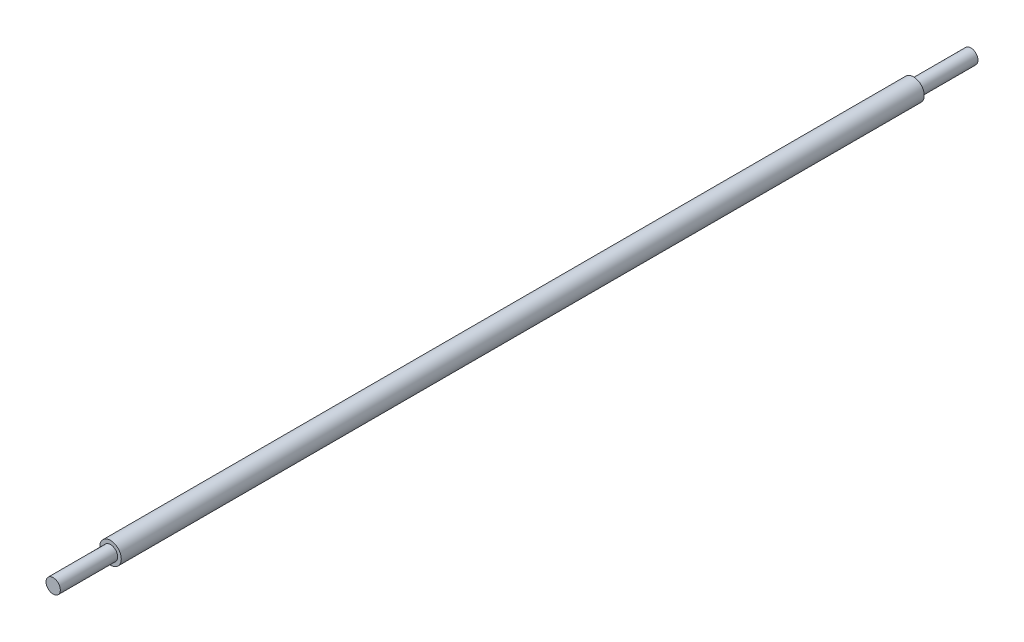
SolidWorks part; units mm, degrees
ref_plane "Front Plane" through (0, 0, 0) normal (0, 0, 1) x (1, 0, 0)
ref_plane "Top Plane" through (0, 0, 0) normal (0, 1, 0) x (1, 0, 0)
ref_plane "Right Plane" through (0, 0, 0) normal (1, 0, 0) x (0, 0, -1)
sketch "Sketch1" plane through (0, 0, 0) normal (0, 0, 1) x (1, 0, 0)
  circle A0 centre (0, 0) radius 2.3813
  dimension "D1" = 4.7625
extrude "Boss-Extrude1" add sketch "Sketch1" along normal blind 203.2
sketch "Sketch2" plane through (0, 0, 0) normal (0, 0, -1) x (-1, 0, 0)
  circle A0 centre (0, 0) radius 1.5875
  circle A1 centre (0, 0) radius 2.3813
  dimension "D1" = 3.175
extrude "Cut-Extrude1" cut sketch "Sketch2" against normal blind 12.7
sketch "Sketch3" plane through (0, 0, 203.2) normal (0, 0, 1) x (1, 0, 0)
  circle A0 centre (0, 0) radius 1.5875
  circle A1 centre (0, 0) radius 2.3813
  dimension "D1" = 3.175
extrude "Cut-Extrude2" cut sketch "Sketch3" against normal blind 12.7
